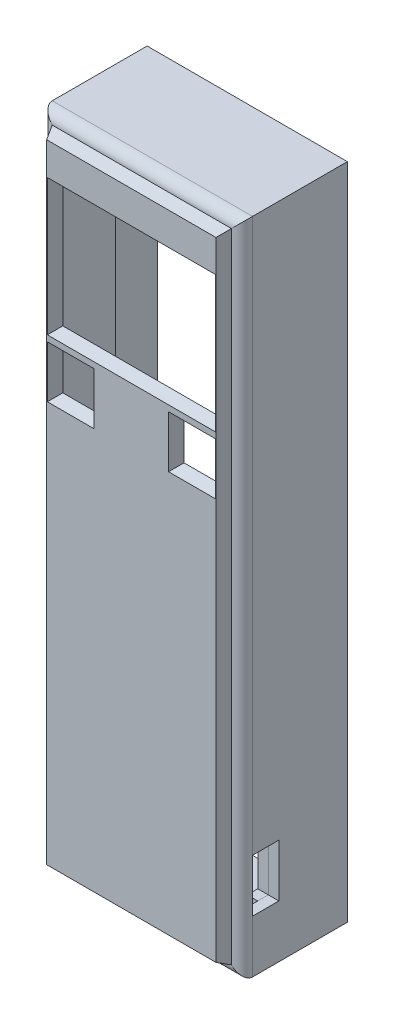
SolidWorks part; units mm, degrees
ref_plane "Plano frontal" through (0, 0, 0) normal (0, 0, 1) x (1, 0, 0)
ref_plane "Plano superior" through (0, 0, 0) normal (0, 1, 0) x (1, 0, 0)
ref_plane "Plano direito" through (0, 0, 0) normal (1, 0, 0) x (0, 0, -1)
sketch "Esboço1" plane through (0, 0, 0) normal (0, 0, 1) x (1, 0, 0)
  line L0 (0, -57) -> (0, 57)
  line L1 (-15, 57) -> (15, 57)
  line L2 (15, 57) -> (15, -57)
  line L3 (15, 0) -> (-15, 0)
  line L4 (-15, 57) -> (-15, -57)
  line L5 (-15, -57) -> (15, -57)
  line L6 (-17, -41) -> (-8, -41)
  line L7 (-17, -52) -> (-8, -52)
  line L8 (-8, 27) -> (-8, 19)
  line L9 (8, -41) -> (17, -41)
  line L10 (8, 27) -> (8, 19)
  line L11 (-8, 57) -> (-8, -57) construction
  line L12 (8, -52) -> (17, -52)
  line L13 (-15, -41) -> (15, -41) construction
  line L14 (-15, 27) -> (15, 27)
  line L15 (-15, -52) -> (15, -52) construction
  line L16 (-15, 19) -> (-8, 19)
  line L17 (8, 19) -> (15, 19)
  line L18 (8, -41) -> (8, -52)
  line L19 (-15, 19) -> (15, 19) construction
  line L20 (-8, -41) -> (-8, -52)
  line L21 (-15, 60) -> (15, 60)
  line L22 (-15, 60) -> (-15, 57)
  line L23 (0, 60) -> (0, 57)
  line L24 (15, 60) -> (15, 57)
  line L25 (5, 60) -> (5, 57)
  line L26 (-5, 60) -> (-5, 57)
  line L27 (-17, 57) -> (-17, -59)
  line L28 (-17, -59) -> (17, -59)
  line L29 (17, 57) -> (17, -59)
  line L30 (17, 62) -> (17, 57)
  line L31 (-17, 62) -> (17, 62)
  line L32 (-17, 62) -> (-17, 57)
  point P8 (0, 0)
  point P16 (8, 57)
  point P17 (8, -57)
sketch "Esboço2" plane through (0, 0, 0) normal (0, 0, 1) x (1, 0, 0)
  line L0 (-8, 27) -> (8, 27)
  line L1 (-17, 62) -> (17, 62)
  line L2 (-17, 62) -> (-17, -59)
  line L3 (-17, -59) -> (17, -59)
  line L4 (17, 62) -> (17, -59)
  line L5 (-15, 27) -> (-8, 27)
  line L6 (-15, 27) -> (-15, 19)
  line L7 (-15, 19) -> (-8, 19)
  line L8 (-8, 27) -> (-8, 19)
  line L9 (8, 19) -> (15, 19)
  line L10 (8, 19) -> (8, 27)
  line L11 (8, 27) -> (15, 27)
  line L12 (15, 19) -> (15, 27)
  line L13 (-8, 30) -> (8, 30)
  line L15 (15, 54) -> (15, 30)
  line L16 (15, 57) -> (15, -57) construction
  line L17 (15, 30) -> (8, 30)
  line L18 (-8, 30) -> (-15, 30)
  line L19 (-15, 57) -> (-15, -57) construction
  line L20 (-15, 30) -> (-15, 54)
  line L21 (-15, 54) -> (15, 54)
extrude "Ressalto-extrusão1" add sketch "Esboço2" along normal blind 2 draft 25 contours L4 L1 L2 L3 L12 L9 L10 L8 L7 L6 L5 L11 L20 L21 L15 L17 L13 L18 region at (0, -8.1185, 0)
sketch "Esboço3" plane through (0, 0, 0) normal (0, 0, 1) x (1, 0, 0)
  line L0 (17, -41) -> (-17, -41)
  line L1 (17, 62) -> (-17, 62)
  line L2 (17, 62) -> (17, -59)
  line L3 (17, -59) -> (-17, -59)
  line L4 (-17, 62) -> (-17, -59)
  line L5 (15, 60) -> (-15, 60)
  line L6 (15, 60) -> (15, -57)
  line L7 (15, -57) -> (-15, -57)
  line L8 (-15, 60) -> (-15, -57)
  line L9 (15, 57) -> (-15, 57)
  line L10 (5, 57) -> (5, 60)
  line L11 (5, 60) -> (-5, 60)
  line L12 (-5, 57) -> (-5, 60)
  line L13 (15, -41) -> (15, -52)
  line L14 (8, -52) -> (17, -52) construction
  line L15 (-17, -52) -> (17, -52)
extrude "Ressalto-extrusão2" add sketch "Esboço3" against normal blind 5 contours L8 L5 L6 L0 L2 L1 L4 | L10 L9 L6 L5 | L9 L12 L5 L8 | L15 L4 L3 L2 L6 L7 L8 region at (16, -39.9153, 0) region at (0, -57.2045, 0) region at (10, 58.5, 0) region at (-10, 58.5, 0)
sketch "Esboço4" plane through (0, 0, -5) normal (0, 0, -1) x (-1, 0, 0)
  line L1 (-17, 62) -> (17, 62)
  line L2 (-17, 62) -> (-17, -59)
  line L3 (-17, -59) -> (17, -59)
  line L4 (17, 62) -> (17, -59)
  line L5 (-15, 60) -> (15, 60)
  line L6 (-15, 60) -> (-15, -57)
  line L7 (-15, -57) -> (15, -57)
  line L8 (15, 60) -> (15, -57)
extrude "Ressalto-extrusão3" add sketch "Esboço4" along normal blind 5
sketch "Esboço5" plane through (0, 0, 0) normal (0, 0, 1) x (1, 0, 0)
  line L0 (-17, 62) -> (17, 62)
  line L1 (17, 62) -> (17, -59)
  line L2 (17, -59) -> (-17, -59)
  line L3 (-17, -59) -> (-17, 62)
  line L4 (-19, -61) -> (-19, 64)
  line L5 (-19, 64) -> (19, 64)
  line L6 (19, 64) -> (19, -61)
  line L7 (19, -61) -> (-19, -61)
  dimension "D1" = 2
extrude "Ressalto-extrusão5" add sketch "Esboço5" against normal blind 20 separate body
fillet "Filete1" radius 2 4 edges at (0, 64, 0) (0, -61, 0) (19, 1.5, 0) (-19, 1.5, 0)
sketch "Esboço6" plane through (-19, 0, 0) normal (-1, 0, 0) x (0, 0, 1)
  line L0 (-2, -61) -> (-2, -41)
  line L1 (-2, -61) -> (-2, 64) construction
  line L2 (-2, -41) -> (-10, -41)
  line L3 (-10, -41) -> (-10, -52)
  line L4 (-10, -51) -> (-2, -51)
  line L5 (-10, -52) -> (-2, -52)
  line L6 (-7, -41) -> (-7, -52)
  dimension "D1" = 1
extrude "Corte-extrusão1" cut sketch "Esboço6" along normal mid plane 132 contours L2 L6 L4 L0 region at (-19, -46, -4.5)
sketch "Esboço7" plane through (-19, 0, 0) normal (-1, 0, 0) x (0, 0, 1)
  line L0 (-20, 64) -> (-2, 64)
  line L1 (-2, 64) -> (-2, -61)
  line L2 (-2, -61) -> (-20, -61)
  line L3 (-20, -61) -> (-20, 64)
  line L4 (-20, 1.5) -> (-2, 1.5)
  line L5 (-2, 1.5) -> (-11, 1.5)
  line L6 (-11, 1.5) -> (-11, 64)
  line L7 (-11, 64) -> (-11, -61)
  line L8 (-11, -61) -> (-11, 1.5)
  line L9 (-11, -29.75) -> (-11, 32.75)
  circle A0 centre (-11, 32.75) radius 1
  circle A1 centre (-11, -29.75) radius 1
